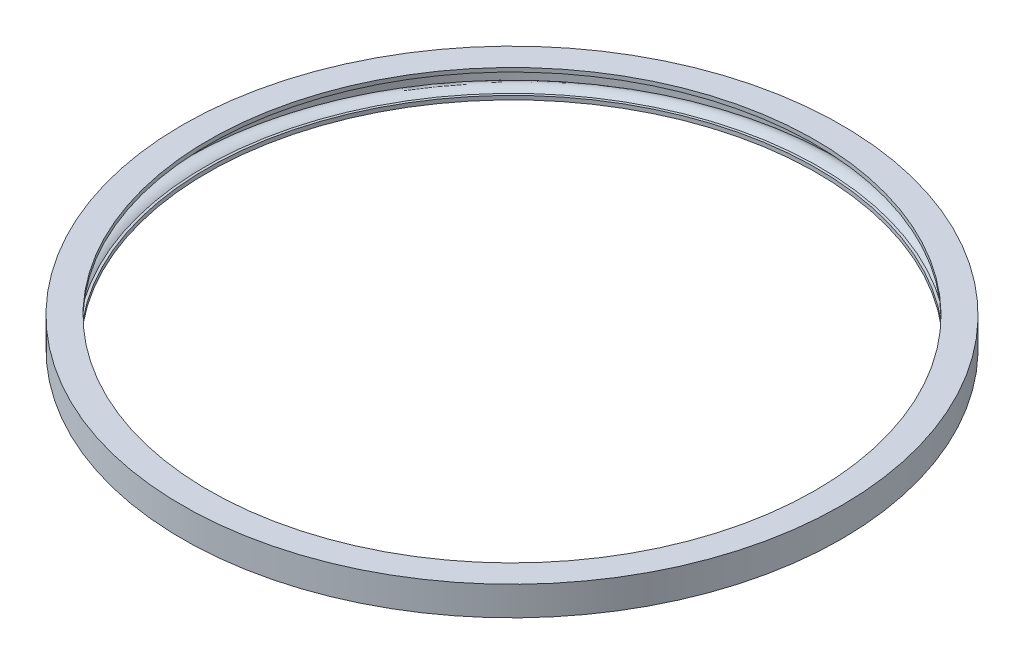
SolidWorks part; units mm, degrees
ref_plane "Front" through (0, 0, 0) normal (0, 0, 1) x (1, 0, 0)
ref_plane "Top" through (0, 0, 0) normal (0, 1, 0) x (1, 0, 0)
ref_plane "Right" through (0, 0, 0) normal (1, 0, 0) x (0, 0, -1)
sketch "Sketch2" plane through (19.1209, -450.557, 65.5706) normal (0.1986, 0, -0.9801) x (-0.9801, 0, -0.1986)
  line L0 (-263.3326, 5.2216) -> (390.7174, 5.2216) construction
  line L1 (-263.3326, 5.2216) -> (63.6924, 5.2216) construction
  line L2 (-253.8076, 8.9005) -> (-253.8076, -16.4995)
  line L3 (-272.8576, 8.9005) -> (-272.8576, -16.4995)
  line L4 (-249.8076, 7.1619) -> (-249.8076, 11.2216)
  line L5 (-249.8076, 11.2216) -> (-219.5385, 11.2216)
  line L6 (-219.5385, 11.2216) -> (-276.8576, 11.2216)
  line L7 (-276.8576, 11.2216) -> (-276.8576, -18.8205)
  line L8 (-276.8576, -18.8205) -> (-251.2782, -18.8205)
  line L9 (-251.2782, -18.8205) -> (-251.2782, -14.7608)
  line L10 (-272.8576, -3.7995) -> (-253.8076, -3.7995) construction
  line L11 (-263.3326, -3.7995) -> (-263.3326, -18.8205) construction
  line L12 (-263.3326, -3.7995) -> (-263.3326, 11.2216) construction
  line L13 (-251.2782, -14.7608) -> (-253.8076, -14.7608)
  line L14 (-249.8076, 7.1619) -> (-253.8076, 7.1619)
  line L15 (63.6924, 5.2216) -> (63.6924, 39.475) construction
  line L16 (63.6924, -18.7995) -> (63.6924, 49.1889) construction
  arc A0 (-263.3326, -12.8205) -> (-272.8576, -16.4995) centre (-263.3326, -26.9903) ccw construction
  arc A1 (-253.8076, -16.4995) -> (-263.3326, -12.8205) centre (-263.3326, -26.9903) ccw construction
  arc A2 (-263.3326, 5.2216) -> (-253.8076, 8.9005) centre (-263.3326, 19.3914) ccw construction
  arc A3 (-272.8576, 8.9005) -> (-263.3326, 5.2216) centre (-263.3326, 19.3914) ccw construction
  arc A4 (-263.3326, -12.8205) -> (-272.8576, -16.4995) centre (-263.3326, -26.9903) ccw
  arc A5 (-253.8076, -16.4995) -> (-263.3326, -12.8205) centre (-263.3326, -26.9903) ccw
  arc A6 (-263.3326, 5.2216) -> (-253.8076, 8.9005) centre (-263.3326, 19.3914) ccw
  arc A7 (-272.8576, 8.9005) -> (-263.3326, 5.2216) centre (-263.3326, 19.3914) ccw
  dimension "D1" = 4
  dimension "D2" = 6
  dimension "D3" = 4
revolve "Revolve1" add sketch "Sketch2" angle 360 about L15 region at (272.3478, -444.0066, 116.8797)
